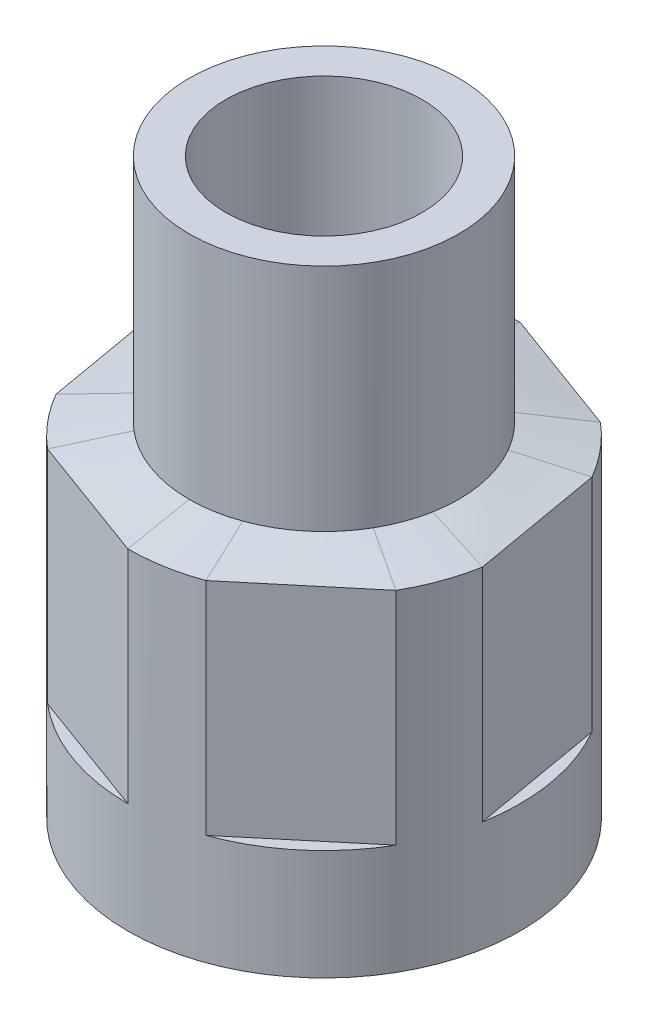
SolidWorks part; units mm, degrees
ref_plane "Спереди" through (0, 0, 0) normal (0, 0, 1) x (1, 0, 0)
ref_plane "Сверху" through (0, 0, 0) normal (0, 1, 0) x (1, 0, 0)
ref_plane "Справа" through (0, 0, 0) normal (1, 0, 0) x (0, 0, -1)
sketch "Эскиз1" plane through (0, 0, 0) normal (0, 1, 0) x (1, 0, 0)
  circle A0 centre (0, 0) radius 11
  dimension "D1" = 22
ref_plane "Плоскость1" through (0, -18.75, 0) normal (0, 1, 0) x (1, 0, 0)
sketch "Эскиз2" plane through (0, -18.75, 0) normal (0, 1, 0) x (1, 0, 0)
  circle A2 centre (0, 0) radius 11
  dimension "D1" = 22
loft "По сечениям1" add profiles "Эскиз2", "Эскиз1" connector at (-7.995, -18.75, -7.5552) connector at (-8.0065, 0, -7.5429)
cosmetic thread "Условное изображение резьбы3" parameters "D2"=20.344
sketch "Эскиз3" plane through (0, 0, 0) normal (0, 1, 0) x (1, 0, 0)
  circle A0 centre (0, 0) radius 8
  circle A1 centre (0, 0) radius 11 construction
  dimension "D1" = 3
extrude "Вырез-Вытянуть1" cut sketch "Эскиз3" against normal blind 12
sketch "Эскиз4" plane through (0, -12, 0) normal (0, 1, 0) x (1, 0, 0)
  circle A0 centre (0, 0) radius 6.5
  circle A1 centre (0, 0) radius 8 construction
  dimension "D1" = 1.5
extrude "Вырез-Вытянуть2" cut sketch "Эскиз4" against normal through all
ref_plane "Плоскость2" through (0, -3.5, 0) normal (0, 1, 0) x (1, 0, 0)
ref_plane "Плоскость3" through (0, -19.75, 0) normal (0, 1, 0) x (1, 0, 0)
sketch "Эскиз6" plane through (0, -19.75, 0) normal (0, 1, 0) x (1, 0, 0)
  line L1 (-5.4169, 15.0551) -> (-13.8564, 8)
  line L2 (-15.7466, 2.8364) -> (-13.8564, -8)
  line L3 (-10.3297, -12.2187) -> (0, -16)
  line L4 (5.4169, -15.0551) -> (13.8564, -8)
  line L5 (15.7466, -2.8364) -> (13.8564, 8)
  line L6 (10.3297, 12.2188) -> (0, 16)
  arc A0 (-13.8564, 8) -> (-15.7466, 2.8364) centre (0, 0) ccw
  circle A1 centre (0, 0) radius 15.025 construction
  arc A2 (-13.8564, -8) -> (-10.3297, -12.2187) centre (0, 0) ccw
  arc A3 (0, 16) -> (-5.4169, 15.0551) centre (0, 0) ccw
  arc A4 (13.8564, 8) -> (10.3297, 12.2188) centre (0, 0) ccw
  arc A5 (13.8564, -8) -> (15.7466, -2.8364) centre (0, 0) ccw
  arc A6 (0, -16) -> (5.4169, -15.0551) centre (0, 0) ccw
  point P3 (-13.8564, 8)
  point P11 (-5.4169, 15.0551)
  point P12 (0, 0)
  point P13 (0, 0)
  point P14 (0, 0)
  dimension "D1" = 32
  dimension "D2" = 11
ref_plane "Плоскость4" through (0, -37.75, 0) normal (0, 1, 0) x (1, 0, 0)
sketch "Эскиз7" plane through (0, -37.75, 0) normal (0, 1, 0) x (1, 0, 0)
  line L0 (-10.3297, -12.2187) -> (0, -16) construction
  line L1 (5.4169, -15.0551) -> (13.8564, -8) construction
  line L2 (15.7466, -2.8364) -> (13.8564, 8) construction
  line L3 (10.3297, 12.2188) -> (0, 16) construction
  line L4 (-5.4169, 15.0551) -> (-13.8564, 8) construction
  line L5 (-15.7466, 2.8364) -> (-13.8564, -8) construction
  line L6 (-10.3297, -12.2187) -> (0, -16)
  line L7 (5.4169, -15.0551) -> (13.8564, -8)
  line L8 (15.7466, -2.8364) -> (13.8564, 8)
  line L9 (10.3297, 12.2188) -> (0, 16)
  line L10 (-5.4169, 15.0551) -> (-13.8564, 8)
  line L11 (-15.7466, 2.8364) -> (-13.8564, -8)
  arc A0 (0, -16) -> (5.4169, -15.0551) centre (0, 0) ccw construction
  arc A1 (13.8564, -8) -> (15.7466, -2.8364) centre (0, 0) ccw construction
  arc A2 (13.8564, 8) -> (10.3297, 12.2188) centre (0, 0) ccw construction
  arc A3 (0, 16) -> (-5.4169, 15.0551) centre (0, 0) ccw construction
  arc A4 (-13.8564, 8) -> (-15.7466, 2.8364) centre (0, 0) ccw construction
  arc A5 (-13.8564, -8) -> (-10.3297, -12.2187) centre (0, 0) ccw construction
  arc A6 (0, -16) -> (5.4169, -15.0551) centre (0, 0) ccw
  arc A7 (13.8564, -8) -> (15.7466, -2.8364) centre (0, 0) ccw
  arc A8 (13.8564, 8) -> (10.3297, 12.2188) centre (0, 0) ccw
  arc A9 (0, 16) -> (-5.4169, 15.0551) centre (0, 0) ccw
  arc A10 (-13.8564, 8) -> (-15.7466, 2.8364) centre (0, 0) ccw
  arc A11 (-13.8564, -8) -> (-10.3297, -12.2187) centre (0, 0) ccw
loft "По сечениям2" add profiles "Эскиз6", "Эскиз2<3>" connector at (15.7466, -19.75, 2.8364) connector at (-8.4845, -18.75, -7.001)
sketch "Эскиз2<3>" plane through (0, -18.75, 0) normal (0, 1, 0) x (1, 0, 0) same geometry as "Эскиз2"
loft "По сечениям3" add profiles "Эскиз7", "Эскиз6<3>" connector at (-13.8564, -37.75, 8) connector at (-13.8564, -19.75, 8)
sketch "Эскиз6<3>" plane through (0, -19.75, 0) normal (0, 1, 0) x (1, 0, 0) same geometry as "Эскиз6"
sketch "Эскиз8" plane through (0, -37.75, 0) normal (0, 1, 0) x (1, 0, 0)
  circle A0 centre (0, 0) radius 16
  dimension "D1" = 32
ref_plane "Плоскость5" through (0, -46.75, 0) normal (0, 1, 0) x (1, 0, 0)
sketch "Эскиз9" plane through (0, -46.75, 0) normal (0, 1, 0) x (1, 0, 0)
  circle A0 centre (0, 0) radius 16 construction
  circle A1 centre (0, 0) radius 16
extrude "Бобышка-Вытянуть1" add sketch "Эскиз8" against normal blind 9 contours A0
ref_plane "Плоскость6" through (0, -47.75, 0) normal (0, 1, 0) x (1, 0, 0)
sketch "Эскиз10" plane through (0, -47.75, 0) normal (0, 1, 0) x (1, 0, 0)
  circle A0 centre (0, 0) radius 13.9
  dimension "D1" = 27.8
extrude "Бобышка-Вытянуть2" add sketch "Эскиз10" along normal blind 1
sketch "Эскиз11" plane through (0, -47.75, 0) normal (0, -1, 0) x (1, 0, 0)
  circle A0 centre (0, 0) radius 10.4585
  dimension "D1" = 20.917
extrude "Вырез-Вытянуть3" cut sketch "Эскиз11" against normal blind 20
sketch "Эскиз12" plane through (0, -27.75, 0) normal (0, -1, 0) x (1, 0, 0)
  circle A0 centre (0, 0) radius 7.4585
  circle A1 centre (0, 0) radius 10.4585 construction
  dimension "D1" = 3
ref_plane "Плоскость7" through (0, -18.75, 0) normal (0, 1, 0) x (1, 0, 0)
extrude "Вырез-Вытянуть4" cut sketch "Эскиз12" against normal up to surface (9 mm away) up to plane "Плоскость7"
